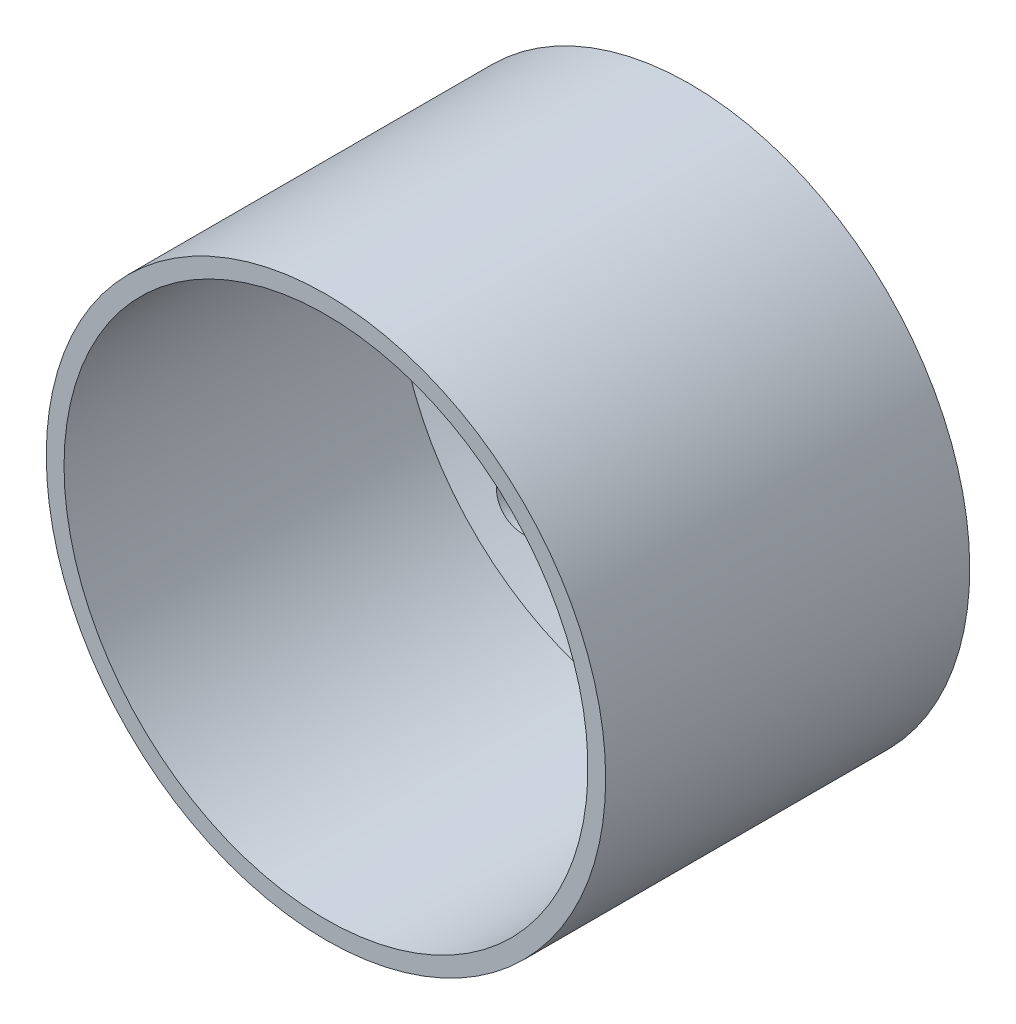
SolidWorks part; units mm, degrees
ref_plane "Front Plane" through (0, 0, 0) normal (0, 0, 1) x (1, 0, 0)
ref_plane "Top Plane" through (0, 0, 0) normal (0, 1, 0) x (1, 0, 0)
ref_plane "Right Plane" through (0, 0, 0) normal (1, 0, 0) x (0, 0, -1)
ref_axis "Z" through (0, 0, -2.5) along (0, 0, 1)
sketch "Sketch1" plane through (0, 0, 0) normal (0, 1, 0) x (1, 0, 0)
  line L0 (31.5, -50) -> (31.5, -9)
  line L1 (0, 5.7328) -> (0, -18.9264) construction
  line L2 (31.5, -9) -> (15, -2)
  line L3 (31.5, -9) -> (31.5, -2) construction
  line L4 (15, -2) -> (31.5, -2) construction
  line L5 (15, -2) -> (9, -2)
  line L6 (9, -2) -> (9, 0)
  line L7 (9, 0) -> (4, 0)
  line L8 (31.5, -50) -> (29.5, -50)
  line L9 (29.5, -50) -> (29.5, -12.4966)
  line L10 (29.5, -12.4966) -> (14.1866, -6)
  line L11 (14.1866, -6) -> (9, -6)
  line L12 (9, -6) -> (9, -10)
  line L13 (9, -10) -> (4, -10)
  line L14 (4, -10) -> (4, 0)
  dimension "D1" = 63
  dimension "D2" = 7
  dimension "D3" = 8
  dimension "D4" = 2
  dimension "D5" = 18
  dimension "D6" = 41
  dimension "D7" = 30
  dimension "D8" = 4
  dimension "D9" = 2
  dimension "D10" = 4
  dimension "D11" = 4
revolve "Revolve1" add sketch "Sketch1" angle 360 about L1
sketch "Sketch3" plane through (0, 0, 2) normal (0, 0, -1) x (-1, 0, 0)
  line L0 (-18, 0) -> (0, 0) construction
  line L1 (0, -54.2514) -> (0, 41.5173) construction
  line L2 (-15.9099, 15.9099) -> (0, 0) construction
  circle A0 centre (-18, 0) radius 8.5
  circle A1 centre (0, 18) radius 8.5
  circle A2 centre (18, 0) radius 8.5
  circle A3 centre (0, -18) radius 8.5
  circle A4 centre (-15.9099, 15.9099) radius 4
  circle A5 centre (15.9099, 15.9099) radius 4
  circle A6 centre (15.9099, -15.9099) radius 4
  circle A7 centre (-15.9099, -15.9099) radius 4
  circle A8 centre (-8.1317, 8.1317) radius 1.5
  circle A9 centre (8.1317, 8.1317) radius 1.5
  circle A10 centre (8.1317, -8.1317) radius 1.5
  circle A11 centre (-8.1317, -8.1317) radius 1.5
  point P15 (0, 0)
  point P24 (0, 0)
  point P33 (0, 0)
  dimension "D10" = 4
  dimension "D1" = 17
  dimension "D4" = 8
  dimension "D8" = 3
  dimension "D2" = 36
  dimension "D5" = 45
  dimension "D6" = 22.5
  dimension "D9" = 11.5
  dimension "D3" = 4
  dimension "D7" = 4
extrude "Cut-Extrude1" cut sketch "Sketch3" against normal through all
equation "\"RotorMainLength\"= 41'rotor body longest dimension"
equation "\"OverallLength\"= 65.8'The height of the whole motor, not counting shaft protrusions"
equation "\"RotorDiameter\"= 63'Overall rotor diameter"
equation "\"RotorTopCapHeight\"= 14'Rough measurement/eyeballed. Not super critical for this; most important dim is overall length"
equation "\"RotorLargeHoleDiameter\"= 17'ID measurement with calipers"
equation "\"RotorLargeHoleTangentSpacing\"= 19'tangent to tangent on the large holes. add one diameter to achieve the center distances"
equation "\"RotorLargeHoleCenterDistance\"= \"RotorLargeHoleTangentSpacing\" + \"RotorLargeHoleDiameter\"'Center to center spacing for large hole"
equation "\"RotorSmallHoleID\"= 8'ID measurement with calipers"
equation "\"RotorSmallHoleTangentSpacing\"= 37'Tangent to Tangent (rounded to the nearest integer, real measurement was like 0.03mm off)"
equation "\"RotorSmallHoleCenterDistance\"= \"RotorSmallHoleID\" + \"RotorSmallHoleTangentSpacing\"'Center to center spacing for small holes"
equation "\"ShaftDiameter\"= 8"
equation "\"RotorShaftTopCapDiameter\"= 18'the small circular extrusion at the top of the rotor"
equation "\"RotorShaftTopCapHeight\"= 2'Height of the small cylindircal extrusion at the top of the rotor"
equation "\"RotorBoltCircleFlatDiameter\"= 30'Diameter of the flat portion where the bolt circle is drilled in the rotor"
equation "\"RotorTaperedEdgeHeight\"= 7'approximate, vertical distance of the tapered/angled edge of the rotor"
equation "\"RotorBoltCircleCenterDistance\"= 23mm'rounded, hard to measure with calipers so assuming they aren't fucking insane and chose this"
equation "\"StatorTrayHeight\"= 3+6+6 'Rough measurement/eyeballed. Not super critical. Take up clearance in airgap; maintain overall height"
equation "\"D1@Sketch1\"=\"RotorDiameter\""
equation "\"D2@Sketch1\"=\"RotorTaperedEdgeHeight\""
equation "\"D3@Sketch1\"=\"ShaftDiameter\""
equation "\"D4@Sketch1\"=\"RotorShaftTopCapHeight\""
equation "\"D5@Sketch1\"=\"RotorShaftTopCapDiameter\""
equation "\"D6@Sketch1\"=\"RotorMainLength\""
equation "\"D7@Sketch1\"=\"RotorBoltCircleFlatDiameter\""
equation "\"D8@Sketch1\"=\"RotorShaftTopCapHeight\"*2"
equation "\"D1@Sketch3\"=\"RotorLargeHoleDiameter\""
equation "\"D2@Sketch3\"=\"RotorLargeHoleCenterDistance\""
equation "\"D4@Sketch3\"=\"RotorSmallHoleID\""
equation "\"D6@Sketch3\"=\"RotorSmallHoleCenterDistance\"/2"
equation "\"D9@Sketch3\"=\"RotorBoltCircleCenterDistance\"/2"
